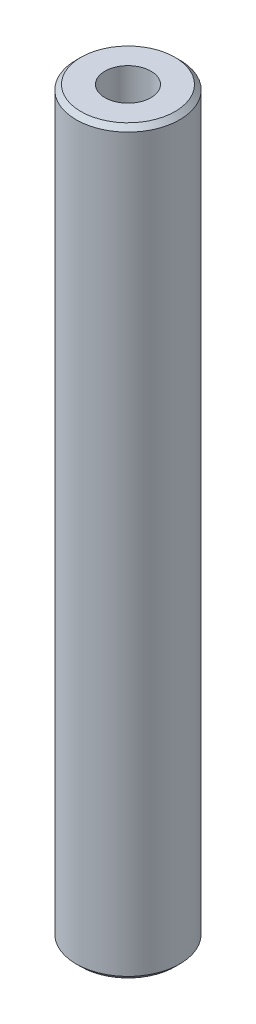
SolidWorks part; units mm, degrees
ref_plane "Front Plane" through (0, 0, 0) normal (0, 0, 1) x (1, 0, 0)
ref_plane "Top Plane" through (0, 0, 0) normal (0, 1, 0) x (1, 0, 0)
ref_plane "Right Plane" through (0, 0, 0) normal (1, 0, 0) x (0, 0, -1)
sketch "Sketch1" plane through (0, 0, 0) normal (0, 1, 0) x (1, 0, 0)
  circle A0 centre (0, 0) radius 7.5
  dimension "SHAFT_OD" = 15
extrude "Boss-Extrude1" add sketch "Sketch1" along normal blind 107.2648
sketch "Sketch2" plane through (0, 0, 0) normal (0, 1, 0) x (1, 0, 0)
  circle A0 centre (0, 0) radius 3.3326
  dimension "BORE_D" = 6.6651
extrude "Cut-Extrude1" cut sketch "Sketch2" along normal through all
chamfer "Chamfer1" distance 0.6869 angle 45 2 edges at (0, 107.2648, 7.5) (0, 0, 7.5)
